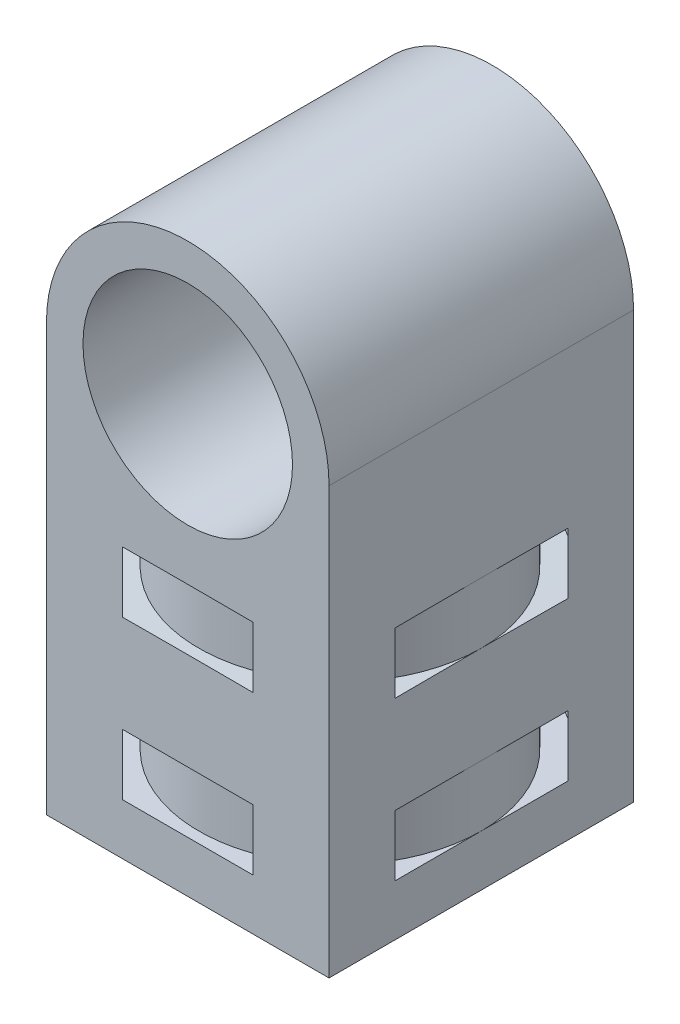
SolidWorks part; units mm, degrees
ref_plane "Alzado" through (0, 0, 0) normal (0, 0, 1) x (1, 0, 0)
ref_plane "Planta" through (0, 0, 0) normal (0, 1, 0) x (1, 0, 0)
ref_plane "Vista lateral" through (0, 0, 0) normal (1, 0, 0) x (0, 0, -1)
sketch "Croquis1" plane through (0, 0, 0) normal (0, 0, 1) x (1, 0, 0)
  line L0 (0, 0) -> (0, -10) construction
  line L1 (-11.6, -10) -> (11.6, -10)
  line L2 (-11.6, -10) -> (-11.6, 0)
  line L3 (11.6, -10) -> (11.6, 0)
  circle A0 centre (0, 0) radius 8.6
  arc A1 (11.6, 0) -> (-11.6, 0) centre (0, 0) ccw
  point P8 (0, -10)
  dimension "D1" = 17.2
  dimension "D2" = 3
  dimension "D3" = 10
extrude "Saliente-Extruir1" add sketch "Croquis1" against normal mid plane 25
ref_plane "Plano1" through (0, -10, 0) normal (0, -1, 0) x (-1, 0, 0)
sketch "Croquis3" plane through (0, -10, 0) normal (0, -1, 0) x (-1, 0, 0)
  line L0 (11.6, -12.5) -> (-11.6, -12.5) construction
  line L1 (11.6, 12.5) -> (11.6, -12.5) construction
  line L2 (-11.6, 12.5) -> (-11.6, -12.5) construction
  line L3 (11.6, 12.5) -> (-11.6, 12.5) construction
  line L4 (11.6, -12.5) -> (-11.6, -12.5)
  line L5 (11.6, 12.5) -> (11.6, -12.5)
  line L6 (-11.6, 12.5) -> (-11.6, -12.5)
  line L7 (11.6, 12.5) -> (-11.6, 12.5)
  circle A0 centre (0, 0) radius 8.6
  dimension "D1" = 17.2
extrude "Saliente-Extruir2" add sketch "Croquis3" along normal blind 25
sketch "Croquis8" plane through (0, 0, 0) normal (0, 0, 1) x (1, 0, 0)
  line L0 (0, -8.6) -> (0, -35) construction
  line L1 (11.6, -35) -> (-11.6, -35) construction
  line L2 (-11.6, 0) -> (-11.6, -35) construction
  line L3 (11.6, -35) -> (11.6, 0) construction
  line L4 (-11.6, -21.8) -> (11.6, -21.8) construction
  line L5 (-13.5998, -17.825) -> (-13.5998, -12.825)
  line L6 (-13.6, -25.8) -> (-11.6, -25.8)
  line L7 (-13.6, -25.8) -> (-13.6, -30.8)
  line L8 (-13.6, -30.8) -> (-11.6, -30.8)
  line L9 (-11.6, -25.8) -> (-11.6, -30.8)
  line L10 (-13.5998, -12.825) -> (-11.6, -12.8)
  line L11 (-13.5998, -17.825) -> (-11.6, -17.8)
  line L12 (-11.6, -17.8) -> (-11.6, -12.8)
  circle A0 centre (0, 0) radius 8.6 construction
  point P8 (0, -21.8)
  point P19 (0, 0)
  point P22 (0, 0)
  point P23 (0, 0)
  dimension "D1" = 26.4
  dimension "D2" = 2
  dimension "D3" = 5
  dimension "D4" = 4
  dimension "D5" = 2
  dimension "D6" = 5
revolve "Cortar-Revolución1" cut sketch "Croquis8" angle 360 about L0 region at (-12.5999, -15.3125, 0) region at (-12.6, -28.3, 0)
